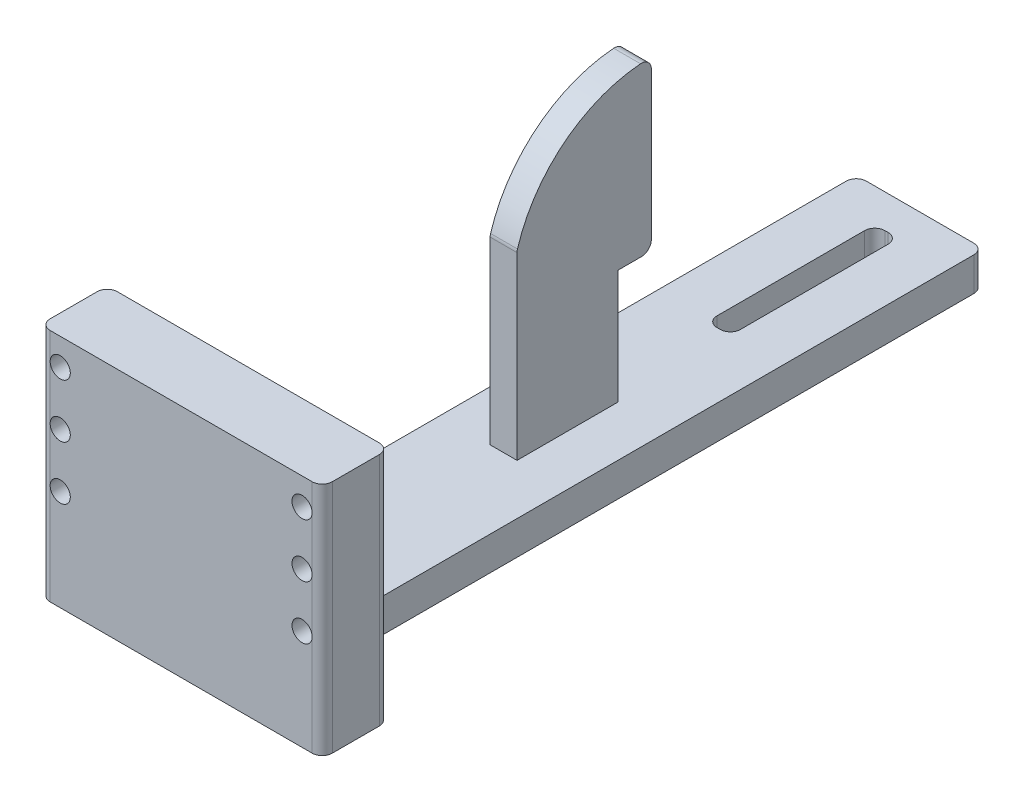
SolidWorks part; units mm, degrees
ref_plane "Front Plane" through (0, 0, 0) normal (0, 0, 1) x (1, 0, 0)
ref_plane "Top Plane" through (0, 0, 0) normal (0, 1, 0) x (1, 0, 0)
ref_plane "Right Plane" through (0, 0, 0) normal (1, 0, 0) x (0, 0, -1)
sketch "Sketch1" plane through (0, 0, 0) normal (0, 1, 0) x (1, 0, 0)
  line L1 (0, 0) -> (-19, 0)
  line L2 (0, 0) -> (0, 110)
  line L3 (0, 110) -> (-19, 110)
  line L4 (-19, 0) -> (-19, 110)
  line L5 (-11.25, 105) -> (-7.75, 105)
  line L6 (-11.25, 105) -> (-11.25, 80)
  line L7 (-11.25, 80) -> (-7.75, 80)
  line L8 (-7.75, 105) -> (-7.75, 80)
  point P9 (-9.5, 105)
  point P10 (-9.5, 110)
  dimension "D1" = 110
  dimension "D2" = 19
  dimension "D3" = 3.5
  dimension "D4" = 5
  dimension "D5" = 25
extrude "Boss-Extrude1" add sketch "Sketch1" along normal blind 5
sketch "Sketch2" plane through (0, 0, 0) normal (1, 0, 0) x (0, 0, -1)
  line L0 (10, 15) -> (10, 35)
  line L2 (0, 5) -> (0, 15)
  line L4 (10, 5) -> (10, 15)
  line L5 (10, 35) -> (0, 35)
  line L6 (0, 35) -> (0, 15)
  line L8 (0, 0) -> (10, 0)
  line L9 (0, 0) -> (0, 5)
  line L11 (10, 0) -> (10, 5)
  line L13 (0, 5) -> (110, 5) construction
  dimension "D1" = 10
  dimension "D2" = 180
  dimension "D3" = 10
  dimension "D4" = 20
  dimension "D5" = 10
extrude "Boss-Extrude2" add sketch "Sketch2" against normal blind 30.5 and the other way blind 11.5
sketch "Sketch3" plane through (0, 0, -10) normal (0, 0, -1) x (-1, 0, 0)
  line L0 (-11.5, 35) -> (30.5, 35) construction
  line L2 (9.5, 35) -> (9.5, 5) construction
  line L3 (19, 5) -> (0, 5) construction
  circle A0 centre (-8.5, 31) radius 1.5
  circle A1 centre (-8.5, 23) radius 1.5
  circle A2 centre (-8.5, 15) radius 1.5
  circle A3 centre (27.5, 15) radius 1.5
  circle A4 centre (27.5, 23) radius 1.5
  circle A5 centre (27.5, 31) radius 1.5
  dimension "D2" = 3
  dimension "D1" = 8
  dimension "D3" = 8
  dimension "D4" = 4
  dimension "D5" = 18
extrude "Cut-Extrude1" cut sketch "Sketch3" against normal blind 10
sketch "Sketch4" plane through (0, 5, 0) normal (0, 1, 0) x (1, 0, 0)
  line L1 (-11.5, 63) -> (-7.5, 63)
  line L2 (-11.5, 63) -> (-11.5, 48)
  line L3 (-11.5, 48) -> (-7.5, 48)
  line L4 (-7.5, 63) -> (-7.5, 48)
  line L5 (0, 110) -> (-19, 110) construction
  line L6 (-19, 10) -> (0, 10) construction
  point P6 (-9.5, 110)
  point P7 (-9.5, 63)
  dimension "D1" = 4
  dimension "D2" = 15
  dimension "D3" = 53
extrude "Boss-Extrude3" add sketch "Sketch4" along normal blind 17
sketch "Sketch5" plane through (-7.5, 0, 0) normal (1, 0, 0) x (0, 0, -1)
  line L0 (63, 22) -> (68, 22)
  line L1 (68, 22) -> (68, 47)
  line L2 (68, 47) -> (78.519, 47) construction
  line L3 (48, 22) -> (63, 22)
  line L4 (48, 22) -> (48, 32)
  arc A0 (48, 32) -> (68, 47) centre (68, 26.1667) cw
  point P9 (48, 34.6274)
  dimension "D1" = 5
  dimension "D2" = 25
  dimension "D3" = 10
extrude "Boss-Extrude4" add sketch "Sketch5" against normal blind 4
fillet "Fillet1" radius 1.5 16 edges at (0, 2.5, -110) (-19, 2.5, -110) (11.5, 17.5, 0) (-30.5, 17.5, 0) (11.5, 17.5, -10) (0, 2.5, -10) (-19, 2.5, -10) (-30.5, 17.5, -10) (-11.25, 2.5, -105) (-7.75, 2.5, -105) (-7.75, 2.5, -80) (-11.25, 2.5, -80) (-9.5, 32, -48) (-9.5, 22, -68) (-9.5, 5, -10) (-9.5, 47, -68)
